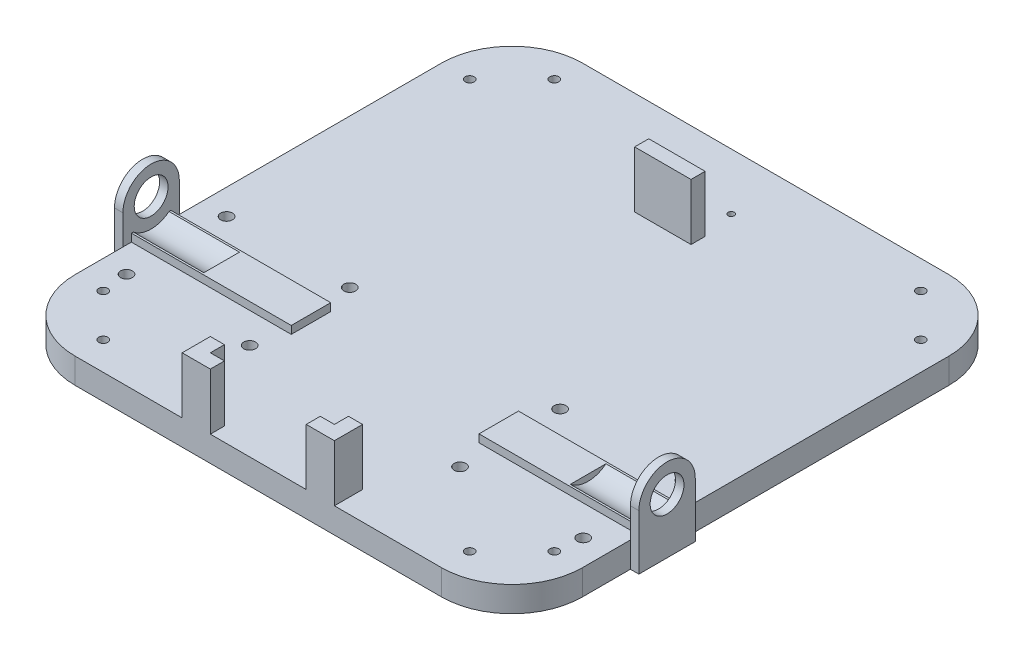
SolidWorks part; units mm, degrees
ref_plane "Front Plane" through (0, 0, 0) normal (0, 0, 1) x (1, 0, 0)
ref_plane "Top Plane" through (0, 0, 0) normal (0, 1, 0) x (1, 0, 0)
ref_plane "Right Plane" through (0, 0, 0) normal (1, 0, 0) x (0, 0, -1)
sketch "Sketch1" plane through (0, 0, 0) normal (0, 1, 0) x (1, 0, 0)
  line L1 (-65, -90) -> (65, -90)
  line L2 (-90, -65) -> (-90, 65)
  line L3 (-65, 90) -> (65, 90)
  line L4 (90, -65) -> (90, 65)
  arc A0 (-90, 65) -> (-65, 90) centre (-65, 65) cw
  arc A1 (65, 90) -> (90, 65) centre (65, 65) cw
  arc A2 (90, -65) -> (65, -90) centre (65, -65) cw
  arc A3 (-65, -90) -> (-90, -65) centre (-65, -65) cw
  point P4 (-90, 0)
  point P6 (0, 90)
  dimension "D3" = 25
  dimension "D1" = 180
  dimension "D2" = 180
extrude "Plate" add sketch "Sketch1" along normal blind 9
sketch "Sketch2" plane through (0, 9, 0) normal (0, 1, 0) x (1, 0, 0)
  line L0 (-7.747, 70) -> (7.747, 70) construction
  line L1 (0, 90) -> (0, 70) construction
  line L2 (-65, 90) -> (65, 90) construction
  circle A1 centre (-7.747, 70) radius 1.095
  circle A2 centre (7.747, 70) radius 1.095
  dimension "D3" = 2.19
  dimension "D1" = 15.494
  dimension "D2" = 20
extrude "Caster Holes" cut sketch "Sketch2" against normal through all
sketch "Sketch3" plane through (0, 9, 0) normal (0, 1, 0) x (1, 0, 0)
  line L0 (-65, 90) -> (-65, -90) construction
  line L1 (65, 90) -> (65, -90) construction
  line L2 (-90, 65) -> (90, 65) construction
  line L3 (-90, -65) -> (90, -65) construction
  circle A0 centre (-65, 80) radius 1.6
  circle A1 centre (-80, 65) radius 1.6
  circle A2 centre (80, 65) radius 1.6
  circle A3 centre (80, -65) radius 1.6
  circle A4 centre (65, 80) radius 1.6
  circle A5 centre (65, -80) radius 1.6
  circle A6 centre (-65, -80) radius 1.6
  circle A7 centre (-80, -65) radius 1.6
  dimension "D1" = 3.2
  dimension "D2" = 15
  dimension "D3" = 15
  dimension "D4" = 15
  dimension "D5" = 15
  dimension "D6" = 15
  dimension "D7" = 15
  dimension "D8" = 15
  dimension "D9" = 15
extrude "Hex Holes" cut sketch "Sketch3" against normal through all
sketch "Sketch4" plane through (0, 9, 0) normal (0, 1, 0) x (1, 0, 0)
  line L0 (-27, -90) -> (-27, -80)
  line L1 (-65, -90) -> (65, -90) construction
  line L2 (-27, -80) -> (-22, -80)
  line L3 (-22, -80) -> (-22, -85)
  line L4 (-22, -85) -> (-17, -85)
  line L5 (-17, -85) -> (-17, -90)
  line L6 (-17, -90) -> (-27, -90)
  line L7 (17, -90) -> (17, -85)
  line L8 (17, -85) -> (22, -85)
  line L9 (22, -85) -> (22, -80)
  line L10 (22, -80) -> (27, -80)
  line L11 (27, -80) -> (27, -90)
  line L12 (27, -90) -> (17, -90)
  line L13 (-10, 58.5) -> (10, 58.5)
  line L14 (10, 58.5) -> (10, 53.5)
  line L15 (10, 53.5) -> (-10, 53.5)
  line L16 (-10, 53.5) -> (-10, 58.5)
  line L17 (-90, -65) -> (-90, 65) construction
  point P20 (0, 53.5)
  dimension "D1" = 5
  dimension "D2" = 44
  dimension "D3" = 63
  dimension "D4" = 20
  dimension "D5" = 5
  dimension "D6" = 138.5
extrude "Battery Holder" add sketch "Sketch4" along normal blind 20
sketch "Sketch5" plane through (0, 9, 0) normal (0, 1, 0) x (1, 0, 0)
  line L0 (-90, -65) -> (-90, 65) construction
  line L1 (-90, -45) -> (-33.3, -45)
  line L2 (-90, -45) -> (-90, -31)
  line L3 (-90, -31) -> (-33.3, -31)
  line L4 (-33.3, -45) -> (-33.3, -31)
  line L5 (90, -65) -> (90, 65) construction
  line L6 (90, -45) -> (33.3, -45)
  line L7 (90, -45) -> (90, -31)
  line L8 (90, -31) -> (33.3, -31)
  line L9 (33.3, -45) -> (33.3, -31)
  line L10 (-65, -90) -> (65, -90) construction
  dimension "D1" = 14
  dimension "D2" = 45
  dimension "D3" = 56.7
extrude "Boss-Extrude2" add sketch "Sketch5" along normal blind 2.75
sketch "Sketch6" plane through (-90, 0, 0) normal (-1, 0, 0) x (0, 0, 1)
  line L0 (31, 11.75) -> (45, 11.75) construction
  line L1 (45, 9) -> (65, 9) construction
  circle A0 centre (38, 19.5) radius 10
  point P5 (38, 11.75)
  dimension "D1" = 20
  dimension "D2" = 10.5
extrude "Cut-Extrude1" cut sketch "Sketch6" against normal blind 25
sketch "Sketch7" plane through (90, 0, 0) normal (1, 0, 0) x (0, 0, -1)
  line L0 (-31, 9) -> (65, 9) construction
  line L1 (-45, 11.75) -> (-31, 11.75) construction
  circle A0 centre (-38, 19.5) radius 10
  point P6 (-38, 11.75)
  dimension "D1" = 20
  dimension "D2" = 10.5
extrude "Cut-Extrude2" cut sketch "Sketch7" against normal blind 25
sketch "Sketch8" plane through (90, 0, 0) normal (1, 0, 0) x (0, 0, -1)
  line L0 (-48, 19.5) -> (-48, 0)
  line L1 (-65, 0) -> (65, 0) construction
  line L2 (-48, 0) -> (-28, 0)
  line L3 (-28, 19.5) -> (-28, 0)
  arc A2 (-28, 19.5) -> (-48, 19.5) centre (-38, 19.5) ccw
  circle A3 centre (-38, 19.5) radius 6
  dimension "D1" = 12
  dimension "D2" = 10
  dimension "D3" = 20
extrude "Boss-Extrude4" add sketch "Sketch8" along normal blind 3
sketch "Sketch9" plane through (-90, 0, 0) normal (-1, 0, 0) x (0, 0, 1)
  line L0 (28, 19.5) -> (28, 0)
  line L1 (65, 0) -> (-65, 0) construction
  line L2 (28, 0) -> (48, 0)
  line L3 (48, 0) -> (48, 19.5)
  circle A0 centre (38, 19.5) radius 6
  arc A1 (48, 19.5) -> (28, 19.5) centre (38, 19.5) ccw
  dimension "D1" = 12
extrude "Boss-Extrude5" add sketch "Sketch9" along normal blind 3
sketch "Sketch10" plane through (0, 9, 0) normal (0, 1, 0) x (1, 0, 0)
  line L0 (90, -65) -> (90, 65) construction
  line L1 (-90, -65) -> (-90, 65) construction
  circle A0 centre (81, -55.75) radius 2.1
  circle A1 centre (81, -20.25) radius 2.1
  circle A2 centre (-81, -20.25) radius 2.1
  circle A3 centre (-81, -55.75) radius 2.1
  circle A4 centre (-37.3, -20.25) radius 2.1
  circle A5 centre (-37.3, -55.75) radius 2.1
  circle A6 centre (37.3, -55.75) radius 2.1
  circle A7 centre (37.3, -20.25) radius 2.1
  dimension "D2" = 4.2
  dimension "D1" = 9.25
  dimension "D3" = 9
  dimension "D4" = 35.5
  dimension "D5" = 9
  dimension "D6" = 43.7
  dimension "D7" = 43.7
extrude "Clamp Holes" cut sketch "Sketch10" against normal through all
